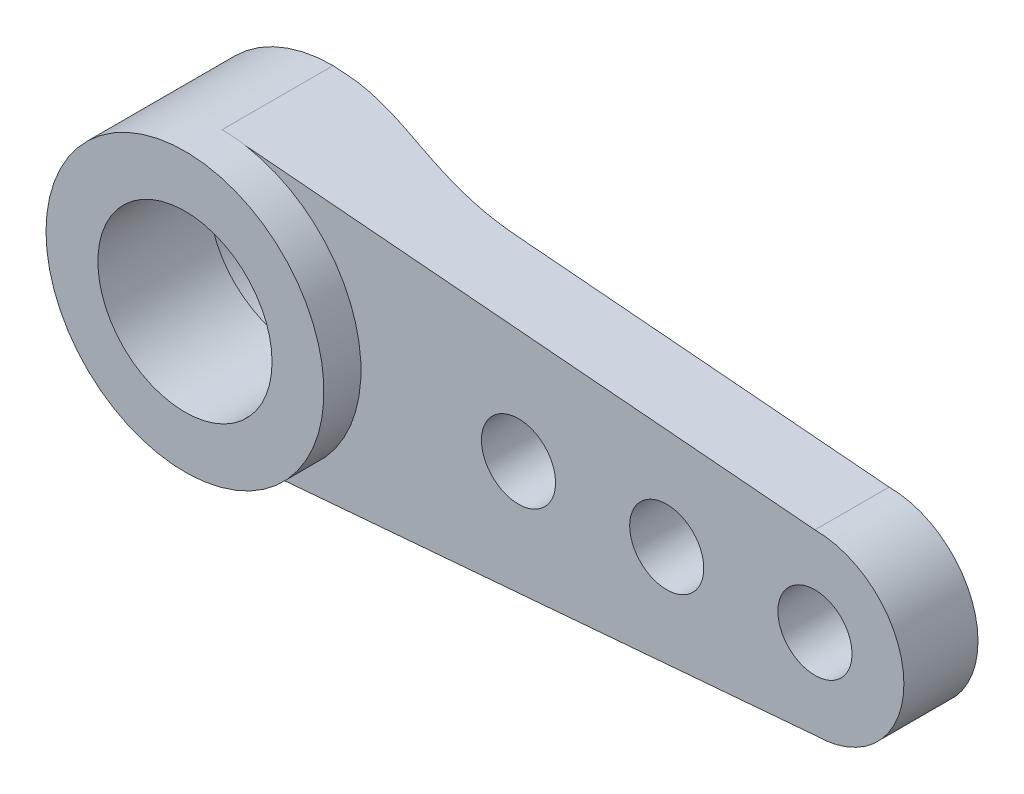
SolidWorks part; units mm, degrees
ref_plane "Front Plane" through (0, 0, 0) normal (0, 0, 1) x (1, 0, 0)
ref_plane "Top Plane" through (0, 0, 0) normal (0, 1, 0) x (1, 0, 0)
ref_plane "Right Plane" through (0, 0, 0) normal (1, 0, 0) x (0, 0, -1)
sketch "Sketch1" plane through (0, 0, 0) normal (0, 0, 1) x (1, 0, 0)
  line L0 (0, 3.75) -> (16, 2.4)
  line L1 (0, -3.75) -> (16, -2.4)
  arc A0 (0.6283, 3.697) -> (0.6283, -3.697) centre (0, 0) ccw
  arc A1 (16, -2.4) -> (16, 2.4) centre (16, 0) ccw
  circle A2 centre (0, 0) radius 2.35
  dimension "D1" = 7.5
  dimension "D2" = 4.8
  dimension "D4" = 4.7
  dimension "D3" = 16
extrude "Boss-Extrude1" add sketch "Sketch1" along normal blind 2 contours L1 A1 L0 A0 A2 region at (7.5625, 0, 0)
sketch "Sketch2" plane through (0, 0, 2) normal (0, 0, 1) x (1, 0, 0)
  line L2 (0, -3.75) -> (16, -2.4)
  line L3 (16, 2.4) -> (0, 3.75)
  circle A0 centre (0, 0) radius 2.35 construction
  circle A1 centre (0, 0) radius 2.35
  arc A2 (16, -2.4) -> (16, 2.4) centre (16, 0) ccw
  arc A3 (0, 3.75) -> (0, -3.75) centre (0, 0) ccw
  arc A5 (0, 3.75) -> (0, -3.75) centre (0, 0) ccw
  arc A6 (0, 3.75) -> (0, -3.75) centre (0, 0) cw
  dimension "D1" = 0
extrude "Boss-Extrude2" add sketch "Sketch2" along normal blind 1
sketch "Sketch3" plane through (0, 0, 0) normal (0, 0, -1) x (-1, 0, 0)
  line L2 (-16, -2.4) -> (0, -3.75)
  line L3 (0, 3.75) -> (-16, 2.4)
  circle A0 centre (0, 0) radius 2.35 construction
  circle A1 centre (0, 0) radius 2.35
  arc A2 (0, -3.75) -> (0, 3.75) centre (0, 0) ccw
  arc A3 (-16, 2.4) -> (-16, -2.4) centre (-16, 0) ccw
  arc A4 (0, -3.75) -> (0, 3.75) centre (0, 0) ccw
  circle A6 centre (0, 0) radius 2.75
  arc A7 (0, 3.75) -> (0, -3.75) centre (0, 0) ccw
  line M6 (-16, -2.4) -> (0, -3.75)
  arc M7 (0, -3.75) -> (0, 3.75) centre (0, 0) ccw
  line M8 (0, 3.75) -> (-16, 2.4)
  dimension "D2" = 5.5
  dimension "D1" = 0
extrude "Boss-Extrude3" add sketch "Sketch3" along normal blind 1 contours A7 A6 M8 M6 M7 region at (3.6439, 0, 0)
fillet "Fillet1" radius 5 1 edges at (3.75, 0, 0)
sketch "Sketch4" plane through (0, 0, 0) normal (0, 0, -1) x (-1, 0, 0)
  line L0 (0, 0) -> (-8, 0) construction
  circle A3 centre (-12, 0) radius 1
  circle A4 centre (-8, 0) radius 1
  circle A5 centre (-16, 0) radius 1
  dimension "D1" = 2
  dimension "D2" = 2
  dimension "D5" = 2
  dimension "D3" = 8
  dimension "D4" = 12
  dimension "D6" = 16
extrude "Cut-Extrude1" cut sketch "Sketch4" against normal up to next contours A5 | A3 | A4 region at (12, 0, 0) region at (8, 0, 0) region at (16, 0, 0)
